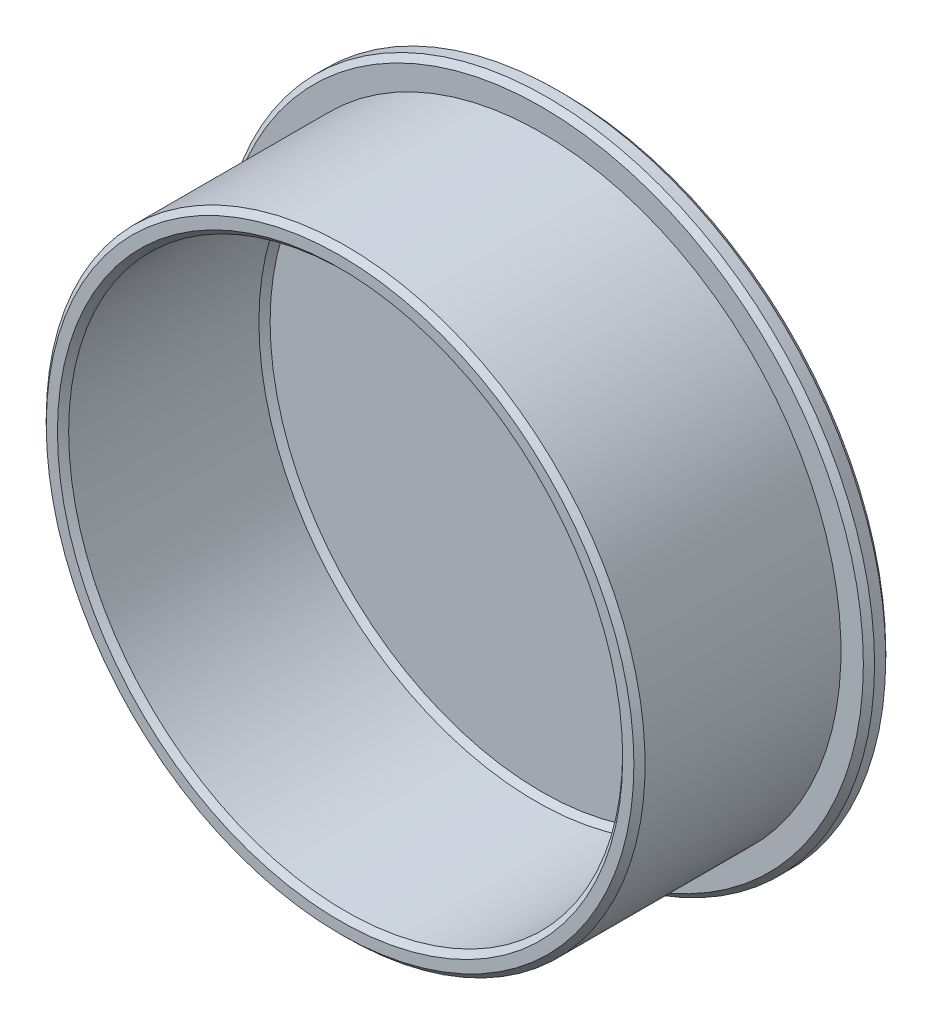
SolidWorks part; units mm, degrees
ref_plane "Front Plane" through (0, 0, 0) normal (0, 0, 1) x (1, 0, 0)
ref_plane "Top Plane" through (0, 0, 0) normal (0, 1, 0) x (1, 0, 0)
ref_plane "Right Plane" through (0, 0, 0) normal (1, 0, 0) x (0, 0, -1)
sketch "Sketch2" plane through (0, 0, 0) normal (0, 0, 1) x (1, 0, 0)
  circle A0 centre (0, 0) radius 29.25
  circle A1 centre (0, 0) radius 26.75
  circle A2 centre (0, 0) radius 24.75
  dimension "D1" = 58.5
  dimension "D2" = 53.5
  dimension "D3" = 2
extrude "Boss-Extrude1" add sketch "Sketch2" along normal blind 2 contours A1 | A0 A1 | A2 region at (-28.4227, 0, 0) region at (-25.9934, 0, 0) region at (0, 0, 0)
extrude "Boss-Extrude2" add sketch "Sketch2<3>" along normal offset from surface (20 mm away) 18 contours A1 region at (-25.9934, 0, 0) up to face at (29.25, 0, 2) offset beyond the face yes
sketch "Sketch2<3>" plane through (0, 0, 0) normal (0, 0, 1) x (1, 0, 0) same geometry as "Sketch2"
chamfer "Chamfer1" distance 0.5 angle 45 5 edges at (29.25, 0, 0) (26.75, 0, 20) (24.75, 0, 20) (29.25, 0, 2) (24.75, 0, 2)
